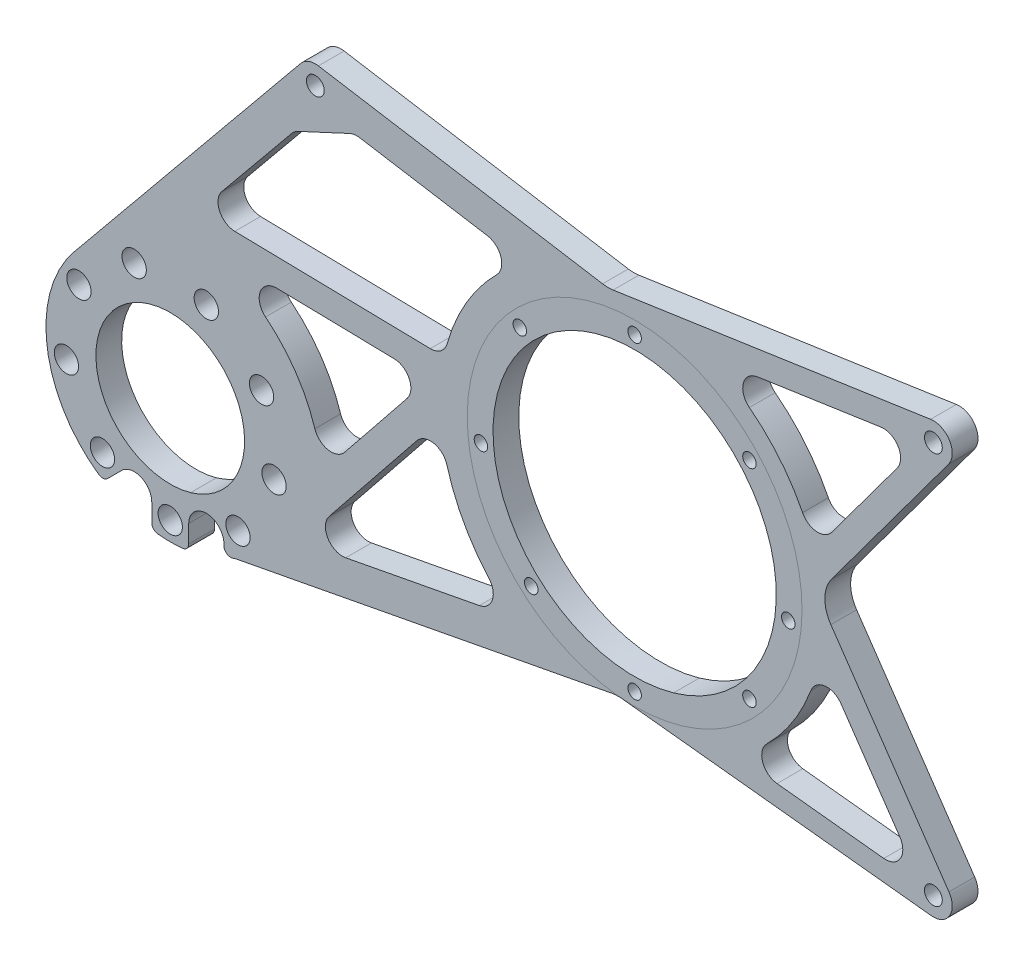
SolidWorks part; units mm, degrees
material "6061-T6 (SS)"
ref_plane "X-Y Datum" through (0, 0, 0) normal (0, 0, 1) x (1, 0, 0)
ref_plane "X-Z Datum" through (0, 0, 0) normal (0, 1, 0) x (1, 0, 0)
ref_plane "Y-Z Datum" through (0, 0, 0) normal (1, 0, 0) x (0, 0, -1)
sketch "Sketch15" plane through (0, 0, 0) normal (0, 0, 1) x (-1, 0, 0)
  line L0 (-666.75, 77.9015) -> (-548.64, 0) construction
  line L1 (-666.75, 77.9015) -> (-494.9785, 127) construction
  line L8 (-471.7786, 164.3167) -> (-477.0435, 159.0518)
  line L9 (-488.1397, 163.648) -> (-488.1397, 170.2207)
  line L10 (-501.8173, 170.2207) -> (-501.8173, 163.648)
  line L11 (-514.8173, 163.648) -> (-514.8173, 164.225)
  line L17 (-660.4, 0) -> (-548.64, 0)
  line L18 (-777.24, 0) -> (-660.4, 0)
  line L19 (-777.24, 145.034) -> (-777.24, 0)
  line L20 (-789.94, 132.334) -> (-764.54, 157.734)
  line L21 (-789.94, 157.734) -> (-764.54, 132.334)
  line L22 (-789.94, 132.334) -> (-764.54, 132.334)
  line L23 (-789.94, 157.734) -> (-764.54, 157.734)
  line L24 (-789.94, 157.734) -> (-789.94, 132.334)
  line L25 (-764.54, 157.734) -> (-764.54, 132.334)
  line L26 (-543.2372, -4.4272) -> (-459.4185, 97.8608)
  line L27 (-777.24, -6.985) -> (-548.64, -6.985)
  line L28 (-784.225, 0) -> (-784.225, 145.034)
  line L29 (-776.4928, 151.9789) -> (-660.1268, 139.4587)
  line L30 (-660.1268, 139.4587) -> (-518.666, 166.4019)
  circle A1 centre (-666.75, 77.9015) radius 52.3875
  circle A4 centre (-548.64, 0) radius 12.7
  circle A5 centre (-777.24, 0) radius 12.7
  arc A16 (-518.666, 166.4019) -> (-468.5208, 164.5979) centre (-494.9785, 127) ccw
  arc A17 (-468.5208, 164.5979) -> (-471.7786, 164.3167) centre (-469.9826, 162.5207) ccw
  arc A18 (-488.1397, 163.648) -> (-477.0435, 159.0518) centre (-481.6397, 163.648) ccw
  arc A19 (-488.1397, 170.2207) -> (-490.4283, 172.7483) centre (-490.6797, 170.2207) ccw
  arc A20 (-490.4283, 172.7483) -> (-499.5287, 172.7483) centre (-494.9785, 127) ccw
  arc A21 (-499.5287, 172.7483) -> (-501.8173, 170.2207) centre (-499.2773, 170.2207) ccw
  arc A22 (-514.8173, 163.648) -> (-501.8173, 163.648) centre (-508.3173, 163.648) ccw
  arc A23 (-514.8173, 164.225) -> (-518.666, 166.4019) centre (-517.3573, 164.225) ccw
  circle A30 centre (-709.2207, 116.1423) radius 2.5
  circle A31 centre (-624.2793, 39.6607) radius 2.5
  circle A33 centre (-709.2207, 39.6607) radius 2.5
  circle A34 centre (-723.5869, 83.8753) radius 2.5
  circle A35 centre (-609.9131, 83.8753) radius 2.5
  circle A36 centre (-666.75, 20.7515) radius 2.5
  arc A40 (-666.75, 132.5515) -> (-666.75, 137.5515) centre (-666.75, 135.0515) ccw
  arc A41 (-666.75, 137.5515) -> (-666.75, 132.5515) centre (-666.75, 135.0515) ccw
  circle A43 centre (-628.5092, 120.3722) radius 2.5
  circle A45 centre (-666.75, 77.9015) radius 61.9125
  circle A46 centre (-548.64, 0) radius 3.3
  circle A47 centre (-777.24, 0) radius 3.3
  circle A48 centre (-777.24, 145.034) radius 3.3
  circle A49 centre (-548.64, 0) radius 6.985
  circle A50 centre (-777.24, 0) radius 6.985
  circle A51 centre (-777.24, 145.034) radius 6.985
  circle A61 centre (-461.2035, 107.5) radius 4.5
  circle A62 centre (-481.6397, 90.352) radius 4.5
  circle A63 centre (-508.3173, 90.352) radius 4.5
  circle A64 centre (-528.7535, 107.5) radius 4.5
  circle A65 centre (-533.386, 133.7723) radius 4.5
  circle A66 centre (-520.0472, 156.8757) radius 4.5
  circle A67 centre (-494.9785, 166) radius 4.5
  circle A68 centre (-469.9098, 156.8757) radius 4.5
  circle A69 centre (-456.571, 133.7723) radius 4.5
  circle A71 centre (-494.9785, 127) radius 27.4955
  dimension "D2" = 6.6
  dimension "D3" = 6.6
  dimension "D4" = 6.6
  dimension "D5" = 13.97
  dimension "D6" = 13.97
  dimension "D7" = 13.97
  dimension "D1" = 141.4871
extrude "Boss-Extrude1" add sketch "Sketch15" along normal blind 9.525 contours A45 A1 A30 A31 A33 A34 A35 A36 A41 A40 A43 | L30 A45 L29 L25 L22 L19 A5 L18 L17 A4 L26 A16 | A51 L21 L25 L29 L20 | A51 L19 L22 L21 | L19 A51 L21 A48 | L20 A51 L19 A48 | A51 L28 L20 | A51 L20 L28 L22 L19 | L21 A51 L20 A48 | A51 L20 A48 L21 | L20 A51 L21 A48 | A51 L20 L29 | A5 L19 L22 L28 | A50 L19 A5 L28 | A50 L18 A5 L19 | A50 L27 A5 L18 | A50 L18 A47 L19 | L18 A50 L19 A47 | A5 L27 A4 L17 L18 | A49 L17 A4 L27 | A49 L26 A4 L17 | A49 A46 | L11 A23 A16 A17 L8 A18 L9 A19 A20 A21 L10 A22 A71 A69 A68 A67 A66 A65 A64 A63 A62 A61 region at (470.0892, -163.7557, 0) region at (621.9919, -118.1022, 0) region at (500.7414, -53.0926, 0) region at (540.1092, 0.1341, 0) region at (545.7357, 6.1347, 0) region at (662.94, 3.5042, 0) region at (557.2397, 3.7525, 0) region at (767.6155, -143.202, 0) region at (768.6403, 3.7525, 0) region at (770.798, -6.442, 0) region at (772.2286, -135.2354, 0) region at (772.7928, -151.1055, 0) region at (782.0394, 4.7994, 0) region at (780.9925, -8.5997, 0) region at (780.7424, -72.1789, 0) region at (773.8261, -3.4139, 0) region at (775.2402, -140.206, 0) region at (772.412, -145.034, 0) region at (780.8486, -135.5958, 0) region at (777.24, -149.862, 0) region at (782.068, -145.034, 0) region at (779.2398, -140.206, 0) region at (783.5955, -140.54, 0)
ref_point "Point1"
ref_point "Point2"
ref_plane "Plane1" through (666.75, -77.9015, 0) normal (-0.9615, -0.2748, 0) x (0, 0, 1)
ref_plane "Plane2" through (494.9785, -127, 0) normal (0.9615, 0.2748, 0) x (0, 0, -1)
split line "Split Line1"
split line "Split Line2"
sketch "Sketch17" plane through (0, 0, 9.525) normal (0, 0, 1) x (1, 0, 0)
  circle A0 centre (666.75, -77.9015) radius 61.9125 construction
  circle A1 centre (666.75, -77.9015) radius 61.9125
split line "Split Line3"
ref_axis "Axis4" through (666.75, -77.9015, 9.525) along (0, 0, -1)
ref_axis "Axis5" through (494.9785, -127, 9.525) along (0, 0, -1)
sketch "Sketch18" plane through (0, 0, 9.525) normal (0, 0, 1) x (1, 0, 0)
  line L4 (514.8173, -163.648) -> (514.8173, -164.225)
  line L5 (501.8173, -170.2207) -> (501.8173, -163.648)
  line L6 (488.1397, -163.648) -> (488.1397, -170.2207)
  line L7 (471.7786, -164.3167) -> (477.0435, -159.0518)
  line L8 (514.8173, -163.648) -> (514.8173, -164.225)
  line L9 (501.8173, -170.2207) -> (501.8173, -163.648)
  line L10 (488.1397, -163.648) -> (488.1397, -170.2207)
  line L11 (471.7786, -164.3167) -> (477.0435, -159.0518)
  line L12 (734.2162, -69.8493) -> (782.8538, -4.1564)
  line L13 (734.2162, -69.8493) -> (783.0031, -141.0872)
  line L14 (776.2216, 6.9104) -> (656.8438, -10.6825)
  line L15 (656.8438, -10.6825) -> (549.7714, 6.8928)
  line L16 (776.4928, -151.9789) -> (687.9549, -142.4528)
  line L17 (776.4928, -151.9789) -> (660.1268, -139.4587) construction
  line L18 (543.2372, 4.4272) -> (459.4185, -97.8608) construction
  line L19 (543.2372, 4.4272) -> (459.4185, -97.8608)
  line L20 (660.1268, -139.4587) -> (518.666, -166.4019) construction
  line L21 (660.1268, -139.4587) -> (518.666, -166.4019)
  circle A0 centre (666.75, -77.9015) radius 67.945
  circle A1 centre (666.75, -77.9015) radius 52.3875
  circle A2 centre (666.75, -77.9015) radius 52.3875
  circle A3 centre (548.64, 0) radius 12.7
  circle A4 centre (548.64, 0) radius 12.7
  circle A5 centre (777.24, 0) radius 12.7
  circle A6 centre (777.24, 0) radius 12.7
  circle A7 centre (777.24, 0) radius 6.985 construction
  circle A8 centre (777.24, -145.034) radius 6.985 construction
  circle A9 centre (548.64, 0) radius 6.985 construction
  arc A10 (514.8173, -164.225) -> (518.666, -166.4019) centre (517.3573, -164.225) ccw
  arc A11 (514.8173, -163.648) -> (501.8173, -163.648) centre (508.3173, -163.648) ccw
  arc A12 (499.5287, -172.7483) -> (501.8173, -170.2207) centre (499.2773, -170.2207) ccw
  arc A13 (490.4283, -172.7483) -> (499.5287, -172.7483) centre (494.9785, -127) ccw
  arc A14 (488.1397, -170.2207) -> (490.4283, -172.7483) centre (490.6797, -170.2207) ccw
  arc A15 (488.1397, -163.648) -> (477.0435, -159.0518) centre (481.6397, -163.648) ccw
  arc A16 (468.5208, -164.5979) -> (471.7786, -164.3167) centre (469.9826, -162.5207) ccw
  arc A17 (518.666, -166.4019) -> (468.5208, -164.5979) centre (494.9785, -127) ccw
  arc A18 (514.8173, -164.225) -> (518.666, -166.4019) centre (517.3573, -164.225) ccw
  arc A19 (514.8173, -163.648) -> (501.8173, -163.648) centre (508.3173, -163.648) ccw
  arc A20 (499.5287, -172.7483) -> (501.8173, -170.2207) centre (499.2773, -170.2207) ccw
  arc A21 (490.4283, -172.7483) -> (499.5287, -172.7483) centre (494.9785, -127) ccw
  arc A22 (488.1397, -170.2207) -> (490.4283, -172.7483) centre (490.6797, -170.2207) ccw
  arc A23 (488.1397, -163.648) -> (477.0435, -159.0518) centre (481.6397, -163.648) ccw
  arc A24 (468.5208, -164.5979) -> (471.7786, -164.3167) centre (469.9826, -162.5207) ccw
  arc A25 (518.666, -166.4019) -> (468.5208, -164.5979) centre (494.9785, -127) ccw
  circle A26 centre (777.24, -145.034) radius 6.985
  circle A27 centre (777.24, 0) radius 6.985
  circle A28 centre (548.64, 0) radius 6.985
  line M37 (784.225, -145.034) -> (784.225, 0)
  line M39 (777.24, 6.985) -> (548.64, 6.985)
  dimension "D5" = 135.89
  dimension "D6" = 65.6929
  dimension "D1" = 0
  dimension "D2" = 0
  dimension "D3" = 0
  dimension "D4" = 0
extrude "Profile" cut sketch "Sketch18" against normal through all contours A6 A4 L15 L14 M39 | A28 L15 A4 M39 | A27 A6 L14 M39 | A26 A6 L12 L13 M37 | A27 L12 A6 M37 region at (660.9586, 1.0495, 9.525) region at (769.684, 6.4437, 9.525) region at (556.2469, 6.3803, 9.525) region at (767.4156, -72.3216, 9.525) region at (781.5837, -8.7535, 9.525)
fillet "Prof Fillet" radius 12.7 3 edges at (660.1268, -139.4587, 4.7625) (734.2162, -69.8493, 4.7625) (656.8438, -10.6825, 4.7625)
sketch "Sketch19" plane through (0, 0, 9.525) normal (0, 0, 1) x (1, 0, 0)
  line L0 (732.9468, -56.6236) -> (772.9791, -2.5535)
  line L1 (772.9791, -2.5535) -> (694.453, -14.126)
  line L2 (776.2216, 6.9104) -> (658.8007, -10.3941) construction
  line L3 (739.5986, -62.5794) -> (782.8538, -4.1564) construction
  line L4 (514.8173, -163.648) -> (514.8173, -164.225)
  line L5 (501.8173, -170.2207) -> (501.8173, -163.648)
  line L6 (488.1397, -163.648) -> (488.1397, -170.2207)
  line L7 (471.7786, -164.3167) -> (477.0435, -159.0518)
  line L8 (514.8173, -163.648) -> (514.8173, -164.225)
  line L9 (501.8173, -170.2207) -> (501.8173, -163.648)
  line L10 (488.1397, -163.648) -> (488.1397, -170.2207)
  line L11 (471.7786, -164.3167) -> (477.0435, -159.0518)
  line L12 (735.3185, -89.4398) -> (772.6135, -143.8976)
  line L13 (772.6135, -143.8976) -> (704.1334, -136.5295)
  line L14 (739.3273, -77.3124) -> (783.0031, -141.0872) construction
  line L15 (776.4928, -151.9789) -> (660.1268, -139.4587) construction
  arc A0 (694.453, -14.126) -> (732.9468, -56.6236) centre (666.75, -77.9015) cw
  circle A1 centre (666.75, -77.9015) radius 52.3875
  circle A2 centre (666.75, -77.9015) radius 52.3875
  circle A3 centre (548.64, 0) radius 12.7
  circle A4 centre (548.64, 0) radius 12.7
  circle A5 centre (777.24, 0) radius 12.7
  circle A6 centre (777.24, 0) radius 12.7
  circle A7 centre (666.75, -77.9015) radius 61.9125 construction
  arc A8 (704.1334, -136.5295) -> (735.3185, -89.4398) centre (666.75, -77.9015) ccw
  arc A10 (514.8173, -164.225) -> (518.666, -166.4019) centre (517.3573, -164.225) ccw
  arc A11 (514.8173, -163.648) -> (501.8173, -163.648) centre (508.3173, -163.648) ccw
  arc A12 (499.5287, -172.7483) -> (501.8173, -170.2207) centre (499.2773, -170.2207) ccw
  arc A13 (490.4283, -172.7483) -> (499.5287, -172.7483) centre (494.9785, -127) ccw
  arc A14 (488.1397, -170.2207) -> (490.4283, -172.7483) centre (490.6797, -170.2207) ccw
  arc A15 (488.1397, -163.648) -> (477.0435, -159.0518) centre (481.6397, -163.648) ccw
  arc A16 (468.5208, -164.5979) -> (471.7786, -164.3167) centre (469.9826, -162.5207) ccw
  arc A17 (518.666, -166.4019) -> (468.5208, -164.5979) centre (494.9785, -127) ccw
  arc A18 (514.8173, -164.225) -> (518.666, -166.4019) centre (517.3573, -164.225) ccw
  arc A19 (514.8173, -163.648) -> (501.8173, -163.648) centre (508.3173, -163.648) ccw
  arc A20 (499.5287, -172.7483) -> (501.8173, -170.2207) centre (499.2773, -170.2207) ccw
  arc A21 (490.4283, -172.7483) -> (499.5287, -172.7483) centre (494.9785, -127) ccw
  arc A22 (488.1397, -170.2207) -> (490.4283, -172.7483) centre (490.6797, -170.2207) ccw
  arc A23 (488.1397, -163.648) -> (477.0435, -159.0518) centre (481.6397, -163.648) ccw
  arc A24 (468.5208, -164.5979) -> (471.7786, -164.3167) centre (469.9826, -162.5207) ccw
  arc A25 (518.666, -166.4019) -> (468.5208, -164.5979) centre (494.9785, -127) ccw
  dimension "D7" = 7.62
  dimension "D8" = 7.62
  dimension "D5" = 8.89
  dimension "D6" = 8.89
  dimension "D9" = 10.16
  dimension "D10" = 7.62
  dimension "D1" = 0
  dimension "D2" = 0
  dimension "D3" = 0
  dimension "D4" = 0
extrude "Cut-Extrude2" cut sketch "Sketch19" against normal through all contours L1 A0 L0 | A8 L13 L12 | L1 A6 L0 | L13 A8 L12 region at (735.5667, -23.3598, 9.525) region at (768.629, -5.1605, 9.525) region at (739.7271, -124.6517, 9.525)
fillet "Fillet2" radius 6.35 6 edges at (694.453, -14.126, 4.7625) (772.9791, -2.5535, 4.7625) (732.9468, -56.6236, 4.7625) (772.6135, -143.8976, 4.7625) (704.1334, -136.5295, 4.7625) (735.3185, -89.4398, 4.7625)
sketch "Sketch22" plane through (0, 0, 9.525) normal (0, 0, 1) x (1, 0, 0)
  line L0 (625.9593, -18.4829) -> (563.0994, -8.1649)
  line L1 (563.0994, -8.1649) -> (540.883, -18.4829)
  line L2 (654.892, -10.3621) -> (549.7714, 6.8928) construction
  line L4 (514.8173, -163.648) -> (514.8173, -164.225)
  line L5 (501.8173, -170.2207) -> (501.8173, -163.648)
  line L6 (488.1397, -163.648) -> (488.1397, -170.2207)
  line L7 (471.7786, -164.3167) -> (477.0435, -159.0518)
  line L8 (514.8173, -163.648) -> (514.8173, -164.225)
  line L9 (501.8173, -170.2207) -> (501.8173, -163.648)
  line L10 (488.1397, -163.648) -> (488.1397, -170.2207)
  line L11 (471.7786, -164.3167) -> (477.0435, -159.0518)
  line L12 (621.3887, -133.9086) -> (542.9827, -148.8422)
  line L13 (542.9827, -148.8422) -> (594.9409, -84.0572)
  line L14 (658.2707, -139.8122) -> (518.666, -166.4019) construction
  line L15 (505.7956, -61.3018) -> (540.883, -18.4829)
  line L16 (540.883, -18.4829) -> (625.9593, -18.4829)
  line L17 (596.2144, -63.0967) -> (505.7956, -61.3018)
  line L18 (543.2372, 4.4272) -> (459.4185, -97.8608) construction
  line L19 (502.7234, -71.4029) -> (590.6658, -73.1486)
  line L20 (590.6658, -73.1486) -> (550.9456, -122.6744)
  arc A0 (594.9409, -84.0572) -> (621.3887, -133.9086) centre (666.75, -77.9015) ccw
  circle A1 centre (666.75, -77.9015) radius 52.3875
  circle A2 centre (666.75, -77.9015) radius 52.3875
  circle A3 centre (548.64, 0) radius 12.7
  circle A4 centre (548.64, 0) radius 12.7
  circle A5 centre (777.24, 0) radius 12.7
  circle A6 centre (777.24, 0) radius 12.7
  circle A7 centre (666.75, -77.9015) radius 61.9125 construction
  arc A8 (625.9593, -18.4829) -> (596.2144, -63.0967) centre (666.75, -77.9015) ccw
  arc A9 (502.7234, -71.4029) -> (550.9456, -122.6744) centre (494.9785, -127) cw
  arc A10 (514.8173, -164.225) -> (518.666, -166.4019) centre (517.3573, -164.225) ccw
  arc A11 (514.8173, -163.648) -> (501.8173, -163.648) centre (508.3173, -163.648) ccw
  arc A12 (499.5287, -172.7483) -> (501.8173, -170.2207) centre (499.2773, -170.2207) ccw
  arc A13 (490.4283, -172.7483) -> (499.5287, -172.7483) centre (494.9785, -127) ccw
  arc A14 (488.1397, -170.2207) -> (490.4283, -172.7483) centre (490.6797, -170.2207) ccw
  arc A15 (488.1397, -163.648) -> (477.0435, -159.0518) centre (481.6397, -163.648) ccw
  arc A16 (468.5208, -164.5979) -> (471.7786, -164.3167) centre (469.9826, -162.5207) ccw
  arc A17 (518.666, -166.4019) -> (468.5208, -164.5979) centre (494.9785, -127) ccw
  arc A18 (514.8173, -164.225) -> (518.666, -166.4019) centre (517.3573, -164.225) ccw
  arc A19 (514.8173, -163.648) -> (501.8173, -163.648) centre (508.3173, -163.648) ccw
  arc A20 (499.5287, -172.7483) -> (501.8173, -170.2207) centre (499.2773, -170.2207) ccw
  arc A21 (490.4283, -172.7483) -> (499.5287, -172.7483) centre (494.9785, -127) ccw
  arc A22 (488.1397, -170.2207) -> (490.4283, -172.7483) centre (490.6797, -170.2207) ccw
  arc A23 (488.1397, -163.648) -> (477.0435, -159.0518) centre (481.6397, -163.648) ccw
  arc A24 (468.5208, -164.5979) -> (471.7786, -164.3167) centre (469.9826, -162.5207) ccw
  arc A25 (518.666, -166.4019) -> (468.5208, -164.5979) centre (494.9785, -127) ccw
  dimension "D6" = 10.16
  dimension "D7" = 10.16
  dimension "D14" = 10.16
  dimension "D5" = 12.7
  dimension "D8" = 12.7
  dimension "D9" = 12.7
  dimension "D10" = 24.4955
  dimension "D11" = 90.4189
  dimension "D12" = 51.9581
  dimension "D13" = 64.7849
  dimension "D15" = 10.16
  dimension "D16" = 10.16
  dimension "D17" = 1.7949
  dimension "D1" = 0
  dimension "D2" = 0
  dimension "D3" = 0
  dimension "D4" = 0
extrude "Cut-Extrude4" cut sketch "Sketch22" against normal through all contours L1 L16 L0 | L17 L15 L16 A8 | L20 A9 L19 | L13 A0 L12 region at (576.6473, -15.0436, 9.525)
fillet "Fillet5" radius 6.35 11 edges at (621.3887, -133.9086, 4.7625) (542.9827, -148.8422, 4.7625) (594.9409, -84.0572, 4.7625) (550.9456, -122.6744, 4.7625) (590.6658, -73.1486, 4.7625) (502.7234, -71.4029, 4.7625) (596.2144, -63.0967, 4.7625) (505.7956, -61.3018, 4.7625) (625.9593, -18.4829, 4.7625) (563.0994, -8.1649, 4.7625) (540.883, -18.4829, 4.7625)
